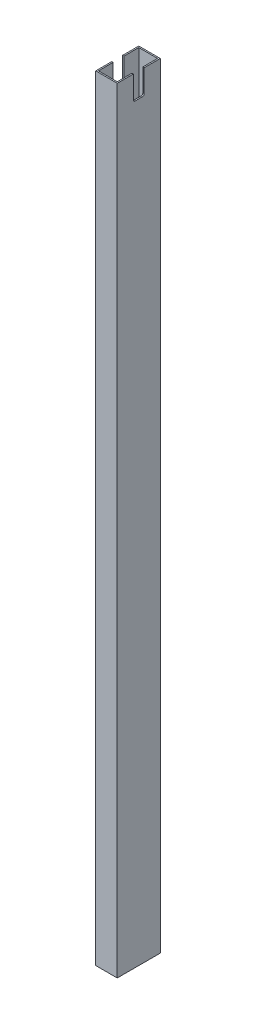
SolidWorks part; units mm, degrees
material "6061-T6 (SS)"
ref_plane "Front" through (0, 0, 0) normal (0, 0, 1) x (1, 0, 0)
ref_plane "Top" through (0, 0, 0) normal (0, 1, 0) x (1, 0, 0)
ref_plane "Right" through (0, 0, 0) normal (1, 0, 0) x (0, 0, -1)
sketch "Sketch1" plane through (0, 0, 0) normal (0, 1, 0) x (1, 0, 0)
  line L1 (12.7, 25.4) -> (-12.7, 25.4)
  line L2 (12.7, 25.4) -> (12.7, -25.4)
  line L3 (12.7, -25.4) -> (-12.7, -25.4)
  line L4 (-12.7, 25.4) -> (-12.7, -25.4)
  line L5 (12.7, 25.4) -> (-12.7, -25.4) construction
  line L6 (12.7, -25.4) -> (-12.7, 25.4) construction
  point P0 (0, 0)
  dimension "D1" = 25.4
  dimension "D2" = 50.8
extrude "Extrude-Thin1" add sketch "Sketch1" along normal blind 914.4 thin thin type one direction reverse wall 1.5875
sketch "Sketch2" plane through (-12.7, 0, 0) normal (-1, 0, 0) x (0, 0, 1)
  line L0 (-25.4, 914.4) -> (25.4, 914.4) construction
  line L1 (-6.35, 914.4) -> (6.35, 914.4)
  line L2 (-6.35, 914.4) -> (-6.35, 887.603)
  line L3 (-4.572, 885.825) -> (4.572, 885.825)
  line L4 (6.35, 914.4) -> (6.35, 887.603)
  line L5 (-25.4, 914.4) -> (-6.35, 885.825) construction
  line L6 (25.4, 914.4) -> (6.35, 885.825) construction
  arc A0 (4.572, 885.825) -> (6.35, 887.603) centre (4.572, 887.603) ccw
  arc A1 (-6.35, 887.603) -> (-4.572, 885.825) centre (-4.572, 887.603) ccw
  dimension "D3" = 1.778
  dimension "D1" = 12.7
  dimension "D2" = 28.575
extrude "Cut-Extrude1" cut sketch "Sketch2" against normal through all
